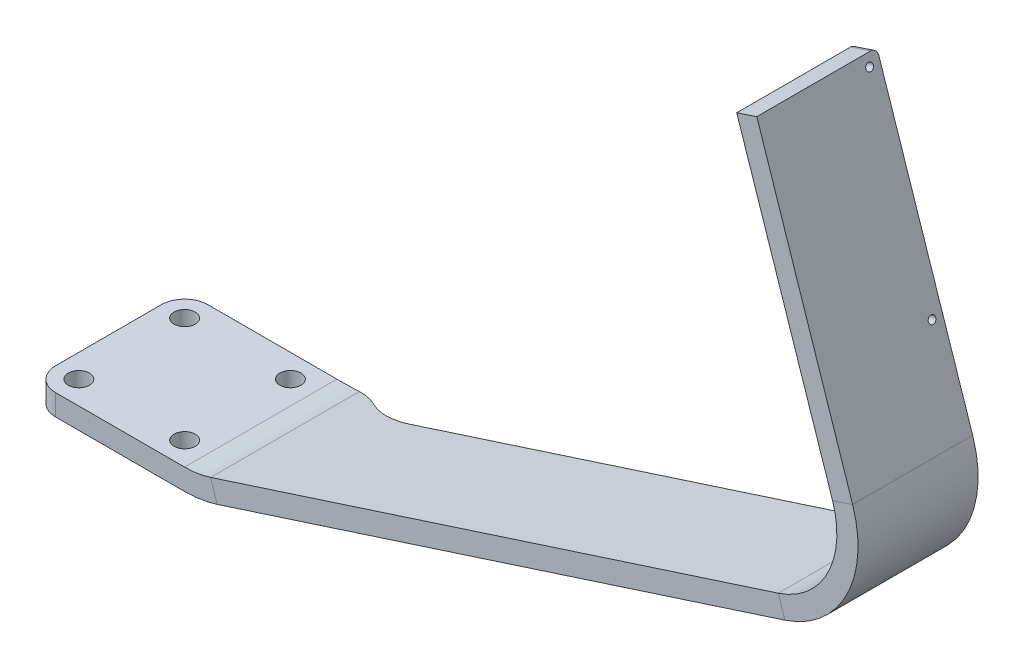
SolidWorks part; units mm, degrees
ref_plane "Front" through (0, 0, 0) normal (0, 0, 1) x (1, 0, 0)
ref_plane "Top" through (0, 0, 0) normal (0, 1, 0) x (1, 0, 0)
ref_plane "Right" through (0, 0, 0) normal (1, 0, 0) x (0, 0, -1)
sketch "Sketch2" plane through (0, 0, 0) normal (0, 1, 0) x (1, 0, 0)
  line L0 (-18, -12.5) -> (-18, 12.5)
  line L1 (-12.5, -12.5) -> (12.5, -12.5) construction
  line L2 (-12.5, -12.5) -> (-12.5, 12.5) construction
  line L3 (-12.5, 12.5) -> (12.5, 12.5) construction
  line L4 (12.5, -12.5) -> (12.5, 12.5) construction
  line L5 (-12.5, -12.5) -> (12.5, 12.5) construction
  line L6 (-12.5, 12.5) -> (12.5, -12.5) construction
  line L7 (-12.5, -18) -> (12.5, -18)
  line L8 (18, -12.5) -> (18, 12.5)
  line L9 (-12.5, 18) -> (12.5, 18)
  line L10 (12.5, 18) -> (18, 18)
  line L11 (18, 18) -> (18, 12.5)
  line L12 (12.5, -18) -> (18, -18)
  line L13 (18, -18) -> (18, -12.5)
  arc A0 (-18, 12.5) -> (-12.5, 18) centre (-12.5, 12.5) cw
  arc A1 (18, 12.5) -> (12.5, 18) centre (12.5, 12.5) ccw construction
  arc A2 (18, -12.5) -> (12.5, -18) centre (12.5, -12.5) cw construction
  arc A3 (-12.5, -18) -> (-18, -12.5) centre (-12.5, -12.5) cw
  circle A4 centre (-12.5, 12.5) radius 2.5
  circle A5 centre (12.5, 12.5) radius 2.5
  circle A6 centre (12.5, -12.5) radius 2.5
  circle A7 centre (-12.5, -12.5) radius 2.5
  point P0 (0, 0)
  dimension "D1" = 5
  dimension "D2" = 3
  dimension "D3" = 25
extrude "Boss-Extrude1" add sketch "Sketch2" along normal mid plane 5
sketch "Sketch5" plane through (18, 0, 0) normal (1, 0, 0) x (0, 0, -1)
  line L4 (-18, -2.5) -> (18, -2.5)
  line L5 (18, -2.5) -> (18, 2.5)
  line L6 (18, 2.5) -> (-18, 2.5)
  line L7 (-18, 2.5) -> (-18, -2.5)
  line L8 (-18, -2.5) -> (18, -2.5)
  line L9 (18, -2.5) -> (18, 2.5)
  line L10 (18, 2.5) -> (-18, 2.5)
  line L11 (-18, 2.5) -> (-18, -2.5)
  dimension "D1" = 0
sketch "Sketch4" plane through (0, 0, 0) normal (0, 0, 1) x (1, 0, 0)
  line L0 (25.6918, -1.2873) -> (159.8642, 42.098)
  line L1 (175.8935, 73.7789) -> (168, 97.5)
  line L2 (-12.5, -2.5) -> (18, -2.5) construction
  line L3 (18, 2.5) -> (18, -2.5) construction
  line L4 (168, 97.5) -> (-125, 0) construction
  arc A0 (159.8642, 42.098) -> (175.8935, 73.7789) centre (152.1724, 65.8853) ccw
  arc A1 (18, -2.5) -> (25.6918, -1.2873) centre (18, 22.5) ccw
  point P5 (0, 0)
  dimension "D1" = 25
  dimension "D2" = 25
  dimension "D3" = 150
  dimension "D4" = 125
  dimension "D5" = 100
sweep "Sweep2" add profiles "Sketch5" path "Sketch4"
sketch "Sketch11" plane through (175.7174, 58.4725, 0) normal (-0.9488, -0.3157, 0) x (0, 0, 1)
  line L0 (-33.75, 34.4677) -> (18, 34.4677)
  line L1 (-28.75, 39.4677) -> (13, 39.4677)
  line L2 (-28.75, 39.4677) -> (-28.75, 81.2177)
  line L3 (-28.75, 81.2177) -> (13, 81.2177)
  line L4 (13, 39.4677) -> (13, 81.2177)
  line L5 (18, 34.4677) -> (18, 86.2177)
  line L6 (-33.75, 86.2177) -> (18, 86.2177)
  line L7 (-33.75, 34.4677) -> (-33.75, 86.2177)
  line L8 (18, 14.4677) -> (18, 39.4677) construction
  line L9 (-18, 39.4677) -> (18, 39.4677) construction
  dimension "D2" = 41.75
  dimension "D1" = 5
extrude "Boss-Extrude2" add sketch "Sketch11" against normal up to surface (5 mm away) up to face at (171.9468, 85.6394, 0)
sketch "Sketch14" plane through (180.4616, 60.0512, 0) normal (0.9488, 0.3157, 0) x (0, 0, -1)
  line L0 (-13, 39.4677) -> (28.75, 39.4677) construction
  line L1 (28.75, 81.2177) -> (28.75, 39.4677) construction
  line L2 (-13, 81.2177) -> (28.75, 81.2177) construction
  line L3 (-13, 39.4677) -> (-13, 81.2177) construction
  line L4 (-13, 39.4677) -> (28.75, 39.4677)
  line L5 (28.75, 81.2177) -> (28.75, 39.4677)
  line L6 (-13, 81.2177) -> (28.75, 81.2177)
  line L7 (-13, 39.4677) -> (-13, 81.2177)
extrude "Boss-Extrude3" add sketch "Sketch14" against normal offset from surface (1.5 mm away) 3.5
fillet "Fillet1" radius 8 1 edges at (167.2066, 91.9664, -18)
sketch "Sketch18" plane through (175.7174, 58.4725, 0) normal (-0.9488, -0.3157, 0) x (0, 0, 1)
  line L0 (-33.75, 34.4677) -> (18, 86.2177) construction
  line L1 (-7.875, 83.7177) -> (-7.875, 36.9677) construction
  line L2 (-28.75, 86.2177) -> (-28.75, 81.2177) construction
  line L3 (18, 86.2177) -> (-33.75, 86.2177) construction
  circle A0 centre (-7.875, 83.7177) radius 0.875
  circle A1 centre (-7.875, 36.9677) radius 0.875
  point P6 (-7.875, 60.3427)
  point P7 (-7.875, 60.3427)
  point P13 (-28.75, 83.7177)
  dimension "D1" = 1.75
extrude "Cut-Extrude3" cut sketch "Sketch18" against normal through all
sketch "Sketch19" plane through (261.6533, 0, 0) normal (0, 1, 0) x (0, 0, 1)
  line L0 (18, -84.4809) -> (-18, -84.4809) construction
  line L1 (-33.75, -108.4142) -> (-33.75, -92.0746) construction
  line L5 (-10.375, -84.4809) -> (-10.375, -218.6533)
  line L6 (-18, -89.4809) -> (-18, -103.3275) construction
  line L7 (-18, -90.504) -> (-18, -94.2929) construction
  line L9 (-18, -243.6533) -> (-33.75, -243.6533)
  line L10 (-33.75, -243.6533) -> (-33.75, -84.4809)
  line L11 (-33.75, -84.4809) -> (-10.375, -84.4809)
  arc A0 (-10.375, -218.6533) -> (-14.1875, -231.1533) centre (-32.7731, -218.6533) cw
  arc A1 (-18, -243.6533) -> (-14.1875, -231.1533) centre (4.3981, -243.6533) cw
  ellipse E0 centre (-7.875, -92.8639) end of major axis (-7, -92.8639) minor radius 0.2763 construction
  point P0 (-7.875, -92.5876)
  point P3 (-7.875, -92.5876)
  point P4 (-10.375, -222.4576)
  point P5 (-32.7731, -218.6533)
  point P7 (-32.7731, -218.6533)
  dimension "D1" = 2.5
  dimension "D2" = 25
extrude "Cut-Extrude4" cut sketch "Sketch19" against normal through all and the other way up to next
fillet "Fillet2" radius 1.5 3 edges at (164.9163, 96.4738, -10.375) (150.867, 141.0692, -10.375) (151.734, 136.0881, -10.375)
